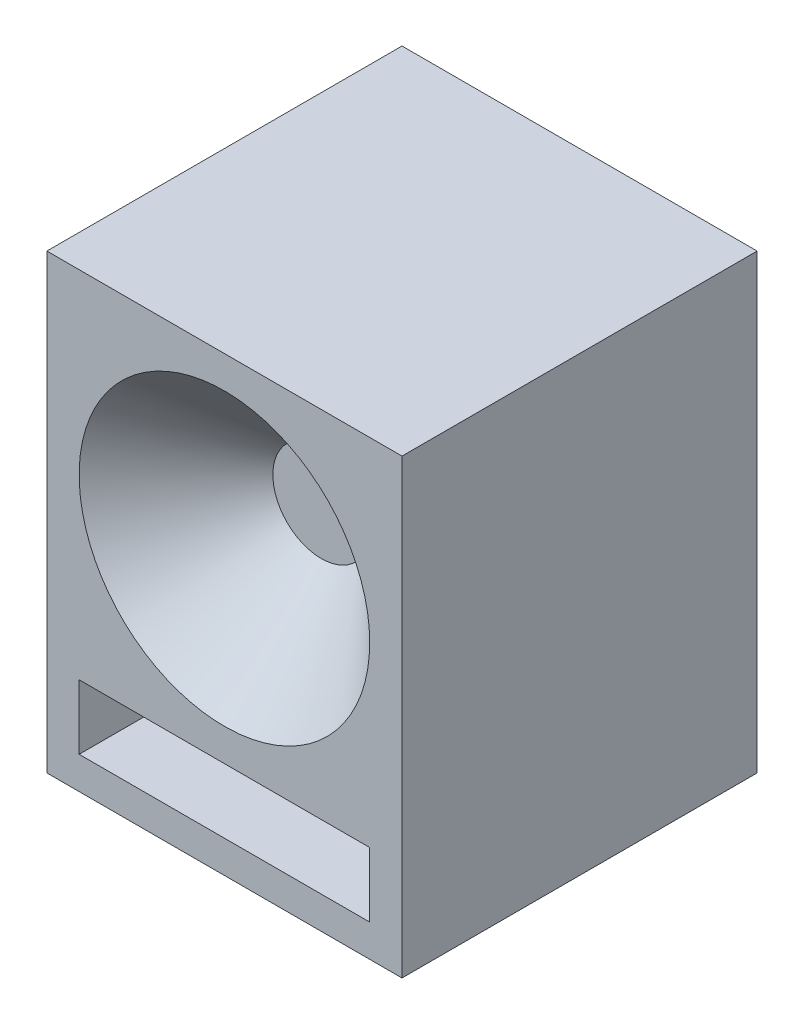
SolidWorks part; units mm, degrees
ref_plane "Front Plane" through (0, 0, 0) normal (0, 0, 1) x (1, 0, 0)
ref_plane "Top Plane" through (0, 0, 0) normal (0, 1, 0) x (1, 0, 0)
ref_plane "Right Plane" through (0, 0, 0) normal (1, 0, 0) x (0, 0, -1)
sketch "Sketch1" plane through (0, 0, 0) normal (0, 0, 1) x (1, 0, 0)
  line L0 (0, 0) -> (0, -76.2) construction
  line L2 (-279.4, -431.8) -> (279.4, -431.8)
  line L3 (-279.4, -431.8) -> (-279.4, 279.4)
  line L4 (-279.4, 279.4) -> (279.4, 279.4)
  line L5 (279.4, -431.8) -> (279.4, 279.4)
  line L6 (-279.4, -431.8) -> (279.4, 279.4) construction
  line L7 (-279.4, 279.4) -> (279.4, -431.8) construction
  circle A0 centre (0, 0) radius 228.6 construction
  dimension "D1" = 457.2
  dimension "D2" = 711.2
  dimension "D3" = 558.8
  dimension "D4" = 76.2
extrude "Boss-Extrude1" add sketch "Sketch1" along normal blind 558.8
sketch "Sketch2" plane through (0, 0, 558.8) normal (0, 0, 1) x (1, 0, 0)
  line L0 (0, 0) -> (0, -330.2) construction
  line L2 (-228.6, -381) -> (228.6, -381)
  line L3 (-228.6, -381) -> (-228.6, -279.4)
  line L4 (-228.6, -279.4) -> (228.6, -279.4)
  line L5 (228.6, -381) -> (228.6, -279.4)
  line L6 (-228.6, -381) -> (228.6, -279.4) construction
  line L7 (-228.6, -279.4) -> (228.6, -381) construction
  circle A0 centre (0, 0) radius 228.6
  dimension "D1" = 457.2
  dimension "D2" = 457.2
  dimension "D3" = 101.6
  dimension "D4" = 330.2
extrude "Cut-Extrude1" cut sketch "Sketch2" against normal blind 152.4
chamfer "Chamfer1" distance 152.4 angle 45 1 edges at (228.6, 0, 406.4)
